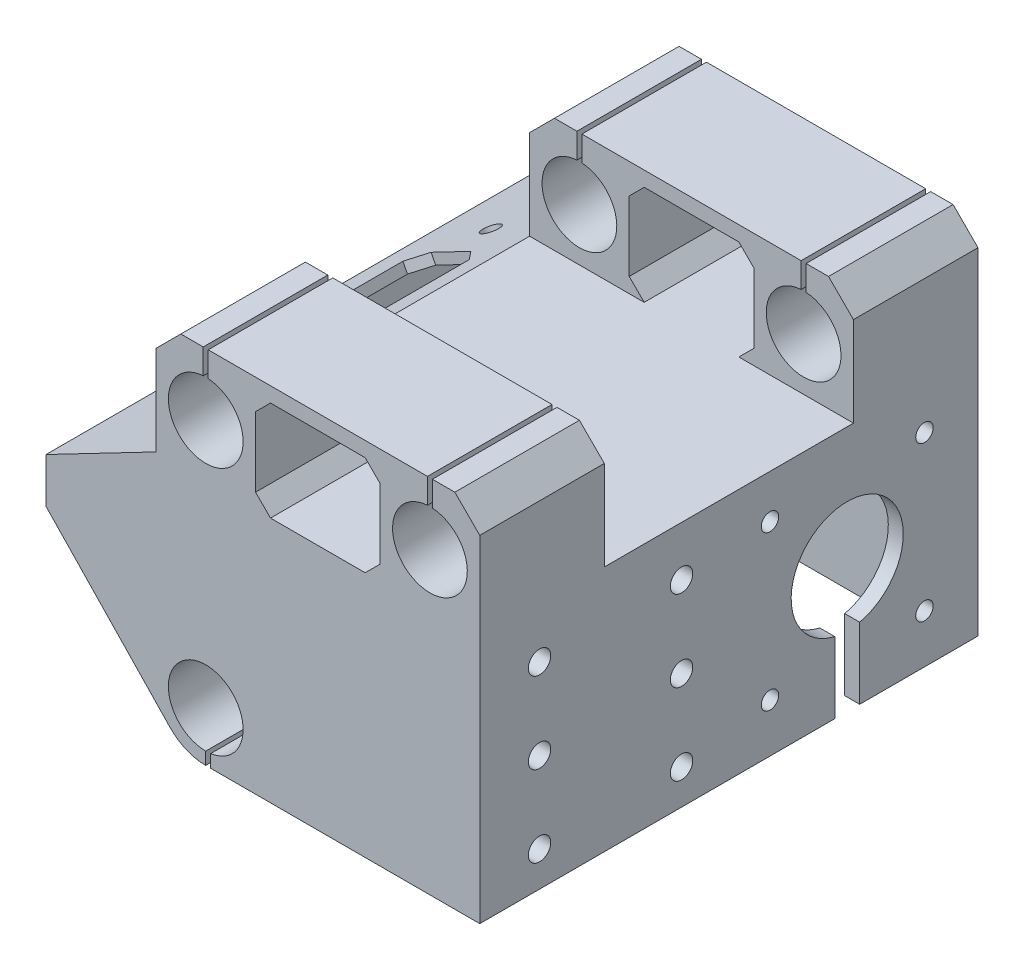
SolidWorks part; units mm, degrees
ref_plane "Front Plane" through (0, 0, 0) normal (0, 0, 1) x (1, 0, 0)
ref_plane "Top Plane" through (0, 0, 0) normal (0, 1, 0) x (1, 0, 0)
ref_plane "Right Plane" through (0, 0, 0) normal (1, 0, 0) x (0, 0, -1)
sketch "Sketch1" plane through (0, 0, 0) normal (0, 0, 1) x (1, 0, 0)
  line L14 (-5, 40) -> (-60, 40)
  line L15 (-60, 40) -> (-65, 35)
  line L16 (-65, 35) -> (-65, -22.5)
  line L17 (-45, -22.5) -> (-45, -17)
  line L18 (-45, -17) -> (0, -17)
  line L19 (0, -17) -> (0, 35)
  line L20 (0, 35) -> (-5, 40)
  line L45 (-45, 34) -> (-45, 20)
  line L46 (-42, 37) -> (-45, 34)
  line L47 (-23, 37) -> (-42, 37)
  line L48 (-20, 34) -> (-23, 37)
  line L49 (-20, 20) -> (-20, 34)
  line L50 (-23, 17) -> (-20, 20)
  line L51 (-42, 17) -> (-23, 17)
  line L52 (-45, 20) -> (-42, 17)
  circle A0 centre (-55, 27.5) radius 7.5
  circle A1 centre (-10, 27.5) radius 7.5
  arc A2 (-65, -22.5) -> (-45, -22.5) centre (-55, -22.5) ccw
  circle A3 centre (-55, -22.5) radius 7.5
  dimension "D1" = 15
extrude "Boss-Extrude1" add sketch "Sketch1" along normal blind 5
sketch "Sketch2" plane through (0, 0, 5) normal (0, 0, 1) x (1, 0, 0)
  line L7 (0, 35) -> (-5, 40)
  line L8 (-5, 40) -> (-60, 40)
  line L9 (-60, 40) -> (-65, 35)
  line L10 (-65, 35) -> (-65, -22.5)
  line L11 (-45, -22.5) -> (-45, -17)
  line L12 (-45, -17) -> (0, -17)
  line L13 (0, -17) -> (0, 35)
  line L14 (0, 35) -> (-5, 40)
  line L15 (-5, 40) -> (-60, 40)
  line L16 (-60, 40) -> (-65, 35)
  line L17 (-65, 35) -> (-65, 14)
  line L20 (0, 14) -> (0, 35)
  line L36 (-65, 14) -> (0, 14)
  line L37 (-32.5, 37) -> (-32.5, 40) construction
  line L38 (-32.5, 17) -> (-32.5, 14) construction
  line L44 (-42, 17) -> (-23, 17)
  line L45 (-45, 20) -> (-42, 17)
  line L46 (-45, 34) -> (-45, 20)
  line L47 (-42, 37) -> (-45, 34)
  line L48 (-23, 37) -> (-42, 37)
  line L49 (-20, 34) -> (-23, 37)
  line L50 (-20, 20) -> (-20, 34)
  line L51 (-23, 17) -> (-20, 20)
  line L52 (-42, 17) -> (-23, 17)
  line L53 (-45, 20) -> (-42, 17)
  line L54 (-45, 34) -> (-45, 20)
  line L55 (-42, 37) -> (-45, 34)
  line L56 (-23, 37) -> (-42, 37)
  line L57 (-20, 34) -> (-23, 37)
  line L58 (-20, 20) -> (-20, 34)
  line L59 (-23, 17) -> (-20, 20)
  arc A1 (-65, -22.5) -> (-45, -22.5) centre (-55, -22.5) ccw
  circle A2 centre (-55, -22.5) radius 7.5
  circle A7 centre (-55, -22.5) radius 10
  circle A10 centre (-55, 27.5) radius 7.5
  circle A11 centre (-55, 27.5) radius 7.5
  circle A12 centre (-10, 27.5) radius 7.5
  circle A13 centre (-10, 27.5) radius 7.5
  circle M22 centre (-10, 27.5) radius 7.5
  line M23 (-23, 17) -> (-42, 17)
  line M24 (-42, 17) -> (-45, 20)
  line M25 (-45, 20) -> (-45, 34)
  line M26 (-45, 34) -> (-42, 37)
  line M27 (-42, 37) -> (-23, 37)
  line M28 (-23, 37) -> (-20, 34)
  line M29 (-20, 34) -> (-20, 20)
  line M30 (-20, 20) -> (-23, 17)
  line M31 (0, 35) -> (-5, 40)
  line M32 (-5, 40) -> (-60, 40)
  line M33 (-60, 40) -> (-65, 35)
  line M34 (-65, 35) -> (-65, -22.5)
  arc M35 (-65, -22.5) -> (-45, -22.5) centre (-55, -22.5) ccw
  circle M39 centre (-55, 27.5) radius 7.5
  circle M40 centre (-55, -22.5) radius 7.5
  dimension "D1" = 0
  dimension "D3" = 0
  dimension "D4" = 0
  dimension "D5" = 0
extrude "Boss-Extrude2" add sketch "Sketch2" along normal blind 20 contours L36 L20 M34 M31 M32 M33 M22 M39 M30 M23 M24 M25 M26 M27 M28 M29 | A7 M35 M40 region at (-0.7001, 24.5, 5) region at (-55, -12.7828, 5)
ref_plane "Plane1" through (0, 0, 50) normal (0, 0, -1) x (-1, 0, 0)
sketch "Sketch3" plane through (0, 0, 25) normal (0, 0, 1) x (1, 0, 0)
  circle A0 centre (-55, -22.5) radius 7.5
  circle A1 centre (-55, -22.5) radius 10
extrude "Boss-Extrude3" add sketch "Sketch3" along normal up to surface (25 mm away) up to plane "Plane1"
mirror "Mirror9" about plane through (0, 0, 50) normal (0, 0, -1) of bodies 104
sketch "Sketch4" plane through (0, 0, 0) normal (1, 0, 0) x (0, 0, -1)
  line L0 (-75, 35) -> (-75, 17)
  line L1 (-100, 35) -> (-75, 35)
  line L2 (-100, 35) -> (-100, -32.5)
  line L3 (-100, -32.5) -> (0, -32.5)
  line L4 (0, 35) -> (0, -32.5)
  line L5 (-25, 35) -> (0, 35)
  line L6 (-25, 17) -> (-25, 35)
  line L7 (-25, 17) -> (-75, 17)
extrude "Boss-Extrude4" add sketch "Sketch4" against normal blind 3
sketch "Sketch5" plane through (0, 0, 25) normal (0, 0, 1) x (1, 0, 0)
  line L0 (-3, 14) -> (-3, 17) construction
  line L1 (-65, 14) -> (-3, 14)
  line L2 (-65, 14) -> (-65, 17)
  line L3 (-65, 17) -> (-3, 17)
  line L4 (-3, 14) -> (-3, 17)
extrude "Boss-Extrude5" add sketch "Sketch5" along normal up to surface (50 mm away) up to face at (-25.125, 26.5, 75)
sketch "Sketch6" plane through (-3, 0, 0) normal (-1, 0, 0) x (0, 0, 1)
  line L0 (95, 14) -> (5, 14) construction
  line L1 (47.5, 14) -> (52.5, 14)
  line L2 (47.5, 14) -> (47.5, -32.5)
  line L3 (47.5, -32.5) -> (52.5, -32.5)
  line L4 (52.5, 14) -> (52.5, -32.5)
  line L5 (5, -17) -> (5, 14) construction
  line L6 (100, -32.5) -> (0, -32.5) construction
  dimension "D1" = 5
  dimension "D2" = 42.5
extrude "Boss-Extrude6" add sketch "Sketch6" along normal up to surface (62 mm away) up to face at (-65, 9.3333, 50)
sketch "Sketch7" plane through (-3, 0, 0) normal (-1, 0, 0) x (0, 0, 1)
  line L0 (5, 14) -> (47.5, -28.5) construction
  line L5 (47.5, 14) -> (47.5, -32.5) construction
  line L6 (10.75, 8.25) -> (41.75, 8.25) construction
  line L7 (41.75, 8.25) -> (41.75, -22.75) construction
  line L8 (41.75, -22.75) -> (10.75, -22.75) construction
  line L9 (10.75, -22.75) -> (10.75, 8.25) construction
  line L10 (10.75, -7.25) -> (26.25, -7.25) construction
  line L11 (26.25, -7.25) -> (26.25, 8.25) construction
  circle A0 centre (26.25, -7.25) radius 11.25
  circle A1 centre (10.75, 8.25) radius 1.75
  circle A2 centre (41.75, 8.25) radius 1.75
  circle A3 centre (41.75, -22.75) radius 1.75
  circle A4 centre (10.75, -22.75) radius 1.75
  dimension "D2" = 22.5
  dimension "D3" = 3.5
  dimension "D1" = 42.5
  dimension "D4" = 31
extrude "Cut-Extrude1" cut sketch "Sketch7" against normal blind 59
sketch "Sketch8" plane through (0, 0, 100) normal (0, 0, 1) x (1, 0, 0)
  line L0 (-65, 16.7374) -> (-90.6831, 2.0239)
  line L1 (-65, 35) -> (-65, -22.5) construction
  line L4 (-65, -32.5) -> (-55, -32.5)
  line L5 (-65, -22.5) -> (-65, -32.5)
  line L6 (-65, -32.5) -> (-55, -32.5)
  line L7 (-65, -22.5) -> (-65, -32.5)
  arc A1 (-65, -22.5) -> (-55, -32.5) centre (-55, -22.5) ccw
  arc A2 (-65, -22.5) -> (-55, -32.5) centre (-55, -22.5) ccw
  arc M9 (-65, -22.5) -> (-45, -22.5) centre (-55, -22.5) ccw
  dimension "D1" = 0
extrude "Cut-Extrude2" cut sketch "Sketch8" against normal blind 146 contours L7 L6 M9 region at (-62.7663, -30.2663, 100)
sketch "Sketch9" plane through (0, 0, 100) normal (0, 0, 1) x (1, 0, 0)
  line L0 (-62.2208, -29.4181) -> (-87.0606, -3.4912)
  line L1 (-87.0606, 5.5183) -> (-65, 17)
  line L3 (-87.0606, 5.5183) -> (-87.0606, -3.4912)
  line L4 (-65, 17) -> (-65, -22.5)
  arc A0 (-65, -22.5) -> (-45, -22.5) centre (-55, -22.5) ccw construction
  arc A1 (-65, -22.5) -> (-62.2208, -29.4181) centre (-55, -22.5) ccw
  line M24 (-65, 35) -> (-65, -22.5)
  arc M25 (-65, -22.5) -> (-45, -22.5) centre (-55, -22.5) ccw
extrude "Boss-Extrude7" add sketch "Sketch9" against normal blind 5 contours L1 L3 L0 M25 M24 region at (-73.5836, -2.5853, 100)
mirror "Mirror10" about plane through (0, 0, 50) normal (0, 0, -1) of "Boss-Extrude7"
sketch "Sketch11" plane through (0, 0, 5) normal (0, 0, 1) x (1, 0, 0)
  line L0 (-65, 17) -> (-87.0606, 5.5183)
  line L1 (-87.0606, 5.5183) -> (-87.0606, -3.4912)
  line L2 (-87.0606, -3.4912) -> (-62.2208, -29.4181)
extrude "Extrude-Thin2" add sketch "Sketch11" along normal up to surface (90 mm away) thin up to face at (-51.9399, -2.9059, 95) thin type one direction reverse wall 2
sketch "Sketch12" plane through (0, 0, 100) normal (0, 0, 1) x (1, 0, 0)
  line L0 (-55, -32.5) -> (-3, -32.5)
  line L1 (-3, -32.5) -> (-3, -17)
  line L2 (-3, -17) -> (-45, -17)
  line L3 (-45, -17) -> (-45, -22.5)
  arc A0 (-62.2208, -29.4181) -> (-45, -22.5) centre (-55, -22.5) ccw construction
  arc A1 (-45, -22.5) -> (-55, -32.5) centre (-55, -22.5) cw
extrude "Boss-Extrude8" add sketch "Sketch12" against normal blind 5
mirror "Mirror11" about plane through (0, 0, 50) normal (0, 0, -1) of "Boss-Extrude8"
sketch "Sketch13" plane through (-20.8164, 39.9959, 0) normal (-0.4617, 0.887, 0) x (0.887, 0.4617, 0)
  line L0 (-49.8097, -50) -> (-74.1166, -50) construction
  line L1 (-49.8097, -75) -> (-49.8097, -25) construction
  line L2 (-57.4631, -30) -> (-54.4631, -33)
  line L3 (-66.4631, -30) -> (-57.4631, -30)
  line L4 (-69.4631, -33) -> (-69.4631, -67)
  line L5 (-66.4631, -70) -> (-57.4631, -70)
  line L6 (-54.4631, -33) -> (-54.4631, -67)
  line L7 (-69.4631, -30) -> (-54.4631, -70) construction
  line L8 (-69.4631, -70) -> (-54.4631, -30) construction
  line L9 (-57.4631, -70) -> (-54.4631, -67)
  line L10 (-69.4631, -67) -> (-66.4631, -70)
  line L11 (-69.4631, -33) -> (-66.4631, -30)
  circle A0 centre (-61.9631, -22) radius 1.75
  circle A1 centre (-61.9631, -78) radius 1.75
  point P4 (-61.9631, -50)
  dimension "D3" = 3.5
  dimension "D4" = 3.5
  dimension "D1" = 40
  dimension "D2" = 15
extrude "Cut-Extrude3" cut sketch "Sketch13" against normal blind 5
sketch "Sketch14" plane through (0, 0, 0) normal (0, 0, -1) x (-1, 0, 0)
  line L0 (55, -22.5) -> (55, -37.8395)
extrude "Cut-Extrude-Thin1" cut sketch "Sketch14" against normal through all both and the other way through all thin thin type one direction wall 1
sketch "Sketch15" plane through (0, 0, 0) normal (0, 0, -1) x (-1, 0, 0)
  circle A0 centre (55, -22.5) radius 7.5
  circle A1 centre (10, 27.5) radius 7.5
  circle A2 centre (55, 27.5) radius 7.5
extrude "Cut-Extrude4" cut sketch "Sketch15" against normal blind 133
sketch "Sketch16" plane through (0, 0, 0) normal (1, 0, 0) x (0, 0, -1)
  line L0 (-26.25, -7.25) -> (-26.25, -40.0284)
extrude "Cut-Extrude-Thin2" cut sketch "Sketch16" against normal blind 7 thin thin type mid plane wall 5
sketch "Sketch17" plane through (0, 0, 100) normal (0, 0, 1) x (1, 0, 0)
  line L0 (-55, 27.5) -> (-55, 46.5746)
  line L1 (-10, 27.5) -> (-10, 46.5746)
extrude "Cut-Extrude-Thin3" cut sketch "Sketch17" against normal blind 116 thin thin type mid plane wall 1
sketch "Sketch18" plane through (-3, 0, 0) normal (-1, 0, 0) x (0, 0, 1)
  line L1 (52.5, 14) -> (95, 14)
  line L2 (52.5, 14) -> (52.5, -32.5)
  line L3 (52.5, -32.5) -> (95, -32.5)
  line L4 (95, 14) -> (95, -32.5)
extrude "Boss-Extrude9" add sketch "Sketch18" along normal blind 5
sketch "Sketch20" plane through (-8, 0, 0) normal (-1, 0, 0) x (0, 0, 1)
  line L0 (59.5, 14) -> (59.5, -32.5) construction
  line L1 (95, 14) -> (52.5, 14) construction
  line L2 (52.5, -32.5) -> (95, -32.5) construction
  line L3 (88, 14) -> (88, -32.5) construction
  circle A0 centre (59.5, 7) radius 2.25
  circle A1 centre (88, 7) radius 2.25
  circle A2 centre (59.5, -9.25) radius 2.25
  circle A3 centre (88, -9.25) radius 2.25
  circle A4 centre (59.5, -25.5) radius 2.25
  circle A5 centre (88, -25.5) radius 2.25
  dimension "D3" = 4.5
  dimension "D1" = 7
  dimension "D2" = 7
  dimension "D4" = 7
  dimension "D5" = 7
  dimension "D6" = 7
  dimension "D7" = 7
extrude "Cut-Extrude6" cut sketch "Sketch20" against normal blind 16
sketch "Sketch21" plane through (-8, 0, 0) normal (-1, 0, 0) x (0, 0, 1)
  line L1 (63.8301, 7) -> (61.6651, 10.75)
  line L2 (61.6651, 10.75) -> (57.3349, 10.75)
  line L3 (57.3349, 10.75) -> (55.1699, 7)
  line L4 (55.1699, 7) -> (57.3349, 3.25)
  line L5 (57.3349, 3.25) -> (61.6651, 3.25)
  line L6 (61.6651, 3.25) -> (63.8301, 7)
  line L7 (63.8301, -9.25) -> (61.6651, -5.5)
  line L8 (61.6651, -5.5) -> (57.3349, -5.5)
  line L9 (57.3349, -5.5) -> (55.1699, -9.25)
  line L10 (55.1699, -9.25) -> (57.3349, -13)
  line L11 (57.3349, -13) -> (61.6651, -13)
  line L12 (61.6651, -13) -> (63.8301, -9.25)
  line L13 (63.8301, -25.5) -> (61.6651, -21.75)
  line L14 (61.6651, -21.75) -> (57.3349, -21.75)
  line L15 (57.3349, -21.75) -> (55.1699, -25.5)
  line L16 (55.1699, -25.5) -> (57.3349, -29.25)
  line L17 (57.3349, -29.25) -> (61.6651, -29.25)
  line L18 (61.6651, -29.25) -> (63.8301, -25.5)
  line L19 (83.6699, -25.5) -> (85.8349, -29.25)
  line L20 (85.8349, -29.25) -> (90.1651, -29.25)
  line L21 (90.1651, -29.25) -> (92.3301, -25.5)
  line L22 (92.3301, -25.5) -> (90.1651, -21.75)
  line L23 (90.1651, -21.75) -> (85.8349, -21.75)
  line L24 (85.8349, -21.75) -> (83.6699, -25.5)
  line L25 (83.6699, -9.25) -> (85.8349, -13)
  line L26 (85.8349, -13) -> (90.1651, -13)
  line L27 (90.1651, -13) -> (92.3301, -9.25)
  line L28 (92.3301, -9.25) -> (90.1651, -5.5)
  line L29 (90.1651, -5.5) -> (85.8349, -5.5)
  line L30 (85.8349, -5.5) -> (83.6699, -9.25)
  line L31 (83.4758, 6.8879) -> (85.6408, 3.1379)
  line L32 (85.6408, 3.1379) -> (89.971, 3.1379)
  line L33 (89.971, 3.1379) -> (92.136, 6.8879)
  line L34 (92.136, 6.8879) -> (89.971, 10.6379)
  line L35 (89.971, 10.6379) -> (85.6408, 10.6379)
  line L36 (85.6408, 10.6379) -> (83.4758, 6.8879)
  circle A0 centre (59.5, 7) radius 3.75 construction
  circle A1 centre (59.5, -9.25) radius 3.75 construction
  circle A2 centre (59.5, -25.5) radius 3.75 construction
  circle A3 centre (88, -25.5) radius 3.75 construction
  circle A4 centre (88, -9.25) radius 3.75 construction
  circle A5 centre (87.8059, 6.8879) radius 3.75 construction
  dimension "D1" = 7.5
extrude "Cut-Extrude7" cut sketch "Sketch21" against normal blind 3
chamfer "Chamfer1" distance 5 angle 45 4 edges at (-48.2918, -15.0838, 47.5) (-48.7505, -14.6934, 95) (-48.2918, -15.0838, 52.5) (-48.7505, -14.6934, 5)
